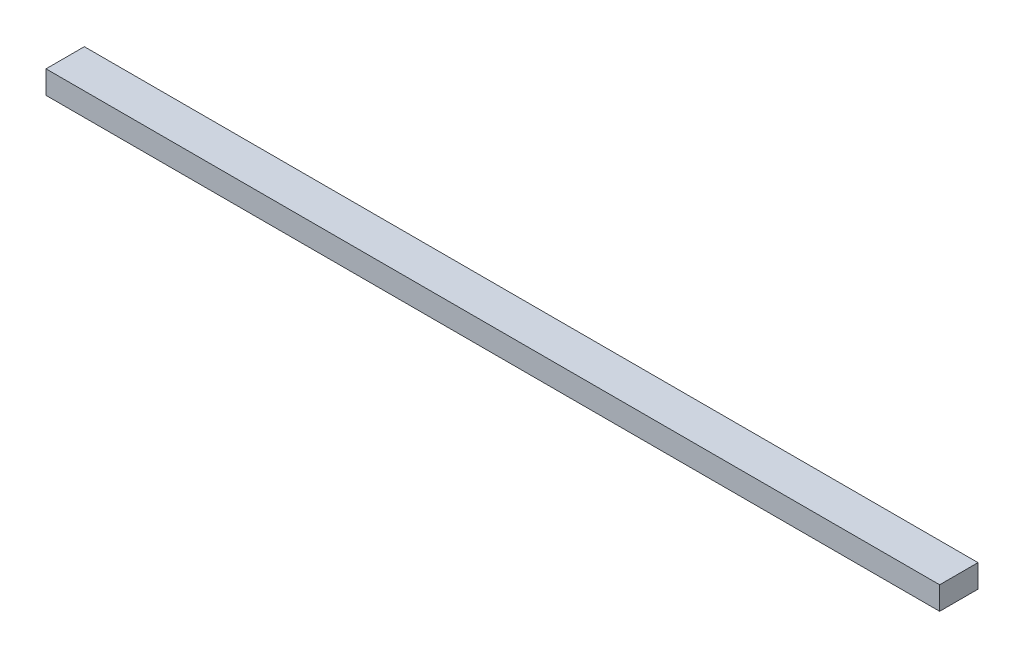
SolidWorks part; units mm, degrees
material "Pine"
ref_plane "Front Plane" through (0, 0, 0) normal (0, 0, 1) x (1, 0, 0)
ref_plane "Top Plane" through (0, 0, 0) normal (0, 1, 0) x (1, 0, 0)
ref_plane "Right Plane" through (0, 0, 0) normal (1, 0, 0) x (0, 0, -1)
sketch "Sketch1" plane through (0, 0, 0) normal (0, 1, 0) x (1, 0, 0)
  line L1 (0, 0) -> (2330, 0)
  line L2 (0, 0) -> (0, 100)
  line L3 (0, 100) -> (2330, 100)
  line L4 (2330, 0) -> (2330, 100)
  dimension "D1" = 100
  dimension "D2" = 2330
extrude "Boss-Extrude1" add sketch "Sketch1" along normal blind 60
